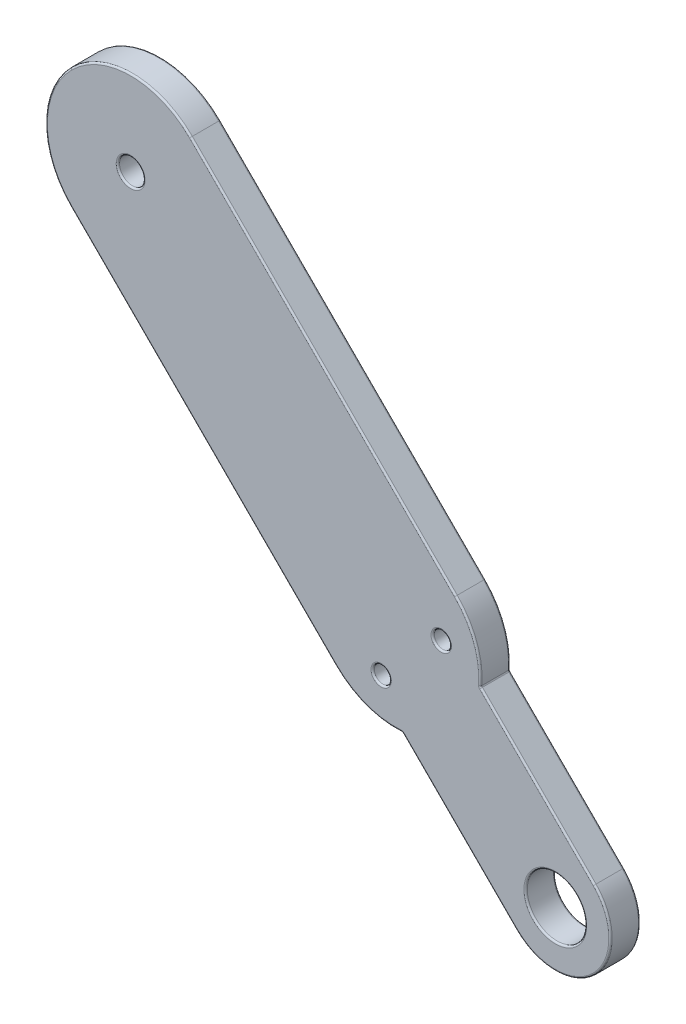
SolidWorks part; units mm, degrees
ref_plane "Front Plane" through (0, 0, 0) normal (0, 0, 1) x (1, 0, 0)
ref_plane "Top Plane" through (0, 0, 0) normal (0, 1, 0) x (1, 0, 0)
ref_plane "Right Plane" through (0, 0, 0) normal (1, 0, 0) x (0, 0, -1)
sketch "Sketch1" plane through (0, 0, 0) normal (0, 0, 1) x (1, 0, 0)
  line L0 (-100, 0) -> (100, 0) construction
  line L1 (-100, 0) -> (0, 100) construction
  line L2 (0, 100) -> (100, 0) construction
  line L3 (0, 0) -> (-50, 50) construction
  line L4 (-50, 50) -> (0, 0) construction
  line L5 (-40, 60) -> (40, 60) construction
  line L6 (0, 100) -> (0, 60) construction
  circle A0 centre (-100, 0) radius 20
  circle A1 centre (0, 0) radius 20
  circle A2 centre (100, 0) radius 20
  point P5 (0, 0)
  dimension "D5" = 40
  dimension "D1" = 200
  dimension "D2" = 90
  dimension "D3" = 90
  dimension "D4" = 80
sketch "Sketch2" plane through (0, 0, 0) normal (0, 0, 1) x (1, 0, 0)
  line L0 (-56.5165, 43.4835) -> (-40, 60) construction
  line L1 (-100, 0) -> (0, 100) construction
  line L2 (-40, 60) -> (40, 60) construction
  line L3 (40, 60) -> (86.565, 13.435) construction
  line L4 (0, 100) -> (100, 0) construction
  line L5 (-49.4454, 36.4124) -> (-35.8579, 50)
  line L6 (-35.8579, 50) -> (35.8579, 50)
  line L7 (35.8579, 50) -> (79.4939, 6.364)
  line L8 (-63.5876, 50.5546) -> (-44.1421, 70)
  line L9 (-44.1421, 70) -> (44.1421, 70)
  line L10 (44.1421, 70) -> (93.636, 20.5061)
  line L11 (-63.5876, 50.5546) -> (-49.4454, 36.4124)
  line L12 (93.636, 20.5061) -> (79.4939, 6.364)
  line L13 (81.9688, 8.8388) -> (95.4038, -4.5962)
  line L14 (91.1612, 18.0312) -> (104.5962, 4.5962)
  line L15 (75.9584, 9.8995) -> (90.1005, 24.0416) construction
  line L16 (0, 100) -> (0, 60) construction
  line L17 (-6, 70) -> (-3.4326, 85.5452)
  line L18 (6, 70) -> (3.4532, 85.4203)
  circle A0 centre (100, 0) radius 3.5
  circle A1 centre (100, 0) radius 10 construction
  arc A2 (95.4038, -4.5962) -> (104.5962, 4.5962) centre (100, 0) ccw
  circle A3 centre (100, 0) radius 0.5
  circle A4 centre (100, 0) radius 6.5 construction
  circle A5 centre (79.4939, 13.435) radius 1.8428
  circle A6 centre (86.565, 20.5061) radius 1.8428
  circle A7 centre (0, 60) radius 1.5
  circle A8 centre (0, 84.85) radius 1.5
  arc A9 (3.4532, 85.4203) -> (-3.4532, 85.4203) centre (0, 84.85) ccw
  circle A10 centre (0, 84.85) radius 3.5 construction
  circle A11 centre (-50, 50) radius 1.5
  dimension "D4" = 20
  dimension "D5" = 7
  dimension "D11" = 3
  dimension "D15" = 3
  dimension "D3" = 27.5
  dimension "D8" = 19
  dimension "D9" = 5
  dimension "D10" = 5
  dimension "5" = 5
  dimension "D12" = 14.85
  dimension "D7" = 6
  dimension "D14" = 6
  dimension "D1" = 10
  dimension "D2" = 10
  dimension "D6" = 3
  dimension "D13" = 2
sketch "Sketch3" plane through (0, 0, 0) normal (0, 0, 1) x (1, 0, 0)
  line L0 (-100, 0) -> (100, 0) construction
  line L1 (-14.1421, 19.799) -> (-12.7279, 21.2132) construction
  line L2 (-21.2132, 12.7279) -> (-19.799, 14.1421) construction
  line L3 (-50, 50) -> (-48.9393, 48.9393) construction
  line L4 (-50, 35.8579) -> (-64.1421, 50)
  line L6 (-50, 35.8579) -> (-20.5061, 6.364)
  line L7 (-64.1421, 50) -> (-50, 64.1421)
  line L8 (-50, 64.1421) -> (-6.364, 20.5061)
  line L9 (-81.6799, 4.1779) -> (-50, 35.8579) construction
  line L10 (-95.8221, 18.3201) -> (-50, 64.1421) construction
  line L12 (-20.5061, 6.364) -> (-18.0312, 8.8388)
  line L15 (-18.0312, 8.8388) -> (-4.5962, -4.5962)
  line L16 (-8.8388, 18.0312) -> (4.5962, 4.5962)
  line L17 (-88.751, 11.249) -> (-50, 50) construction
  line L19 (-8.8388, 18.0312) -> (-6.364, 20.5061)
  line L21 (-51.0607, 48.9393) -> (-50, 50) construction
  line L23 (-50, 50) -> (-13.435, 13.435) construction
  circle A3 centre (0, 0) radius 3.5
  arc A4 (-4.5962, -4.5962) -> (4.5962, 4.5962) centre (0, 0) ccw
  circle A7 centre (0, 0) radius 6.5 construction
  circle A10 centre (-20.5061, 13.435) radius 1
  circle A11 centre (-13.435, 20.5061) radius 1
  circle A12 centre (-50, 50) radius 1.5 construction
  circle A13 centre (-50, 50) radius 1.5
  dimension "D8" = 19
  dimension "D12" = 5
  dimension "D13" = 5
  dimension "D15" = 5
  dimension "D3" = 3
  dimension "D5" = 10
  dimension "D6" = 10
sketch "Sketch4" plane through (0, 0, 0) normal (0, 0, 1) x (1, 0, 0)
  line L1 (57.5, 96.35) -> (57.5, 86.35)
  line L2 (57.5, 86.35) -> (44.1421, 70)
  line L3 (44.1421, 70) -> (-44.1421, 70)
  line L4 (-44.1421, 70) -> (-57.5, 86.35)
  line L5 (-57.5, 86.35) -> (-57.5, 96.35)
  line L7 (-57.5, 96.35) -> (57.5, 96.35)
  line L8 (-4, 60) -> (-4, 70)
  line L9 (4, 60) -> (4, 70)
  line L10 (-22.4799, 87.85) -> (22.5201, 87.85) construction
  line L11 (-22.4799, 92.35) -> (22.5201, 92.35)
  line L12 (-22.4799, 83.35) -> (22.5201, 83.35)
  circle A0 centre (0, 60) radius 1.5 construction
  circle A1 centre (0, 60) radius 1.5
  arc A2 (-4, 60) -> (4, 60) centre (0, 60) ccw
  circle A3 centre (0, 60) radius 4 construction
  arc A4 (-22.4799, 92.35) -> (-22.4799, 83.35) centre (-22.4799, 87.85) ccw
  arc A5 (22.5201, 83.35) -> (22.5201, 92.35) centre (22.5201, 87.85) ccw
  circle A6 centre (0, 84.85) radius 1.5 construction
  point P0 (0, 96.35)
  point P22 (0.0201, 87.85)
  dimension "D1" = 115
  dimension "D2" = 10
  dimension "D4" = 45
  dimension "D5" = 9
  dimension "D6" = 45
  dimension "D7" = 4
  dimension "D3" = 2.5
extrude "Boss-Extrude1" add sketch "Sketch3" along normal blind 3.5
fillet "Fillet1" radius 10 4 edges at (-20.5061, 6.364, 1.75) (-6.364, 20.5061, 1.75) (-64.1421, 50, 1.75) (-50, 64.1421, 1.75)
fillet "Fillet2" radius 0.2 28 edges at (-48.5, 50, 0) (-48.5, 50, 3.5) (-12.435, 20.5061, 0) (-12.435, 20.5061, 3.5) (-19.5061, 13.435, 0) (-19.5061, 13.435, 3.5) (3.5, 0, 0) (3.5, 0, 3.5) (-41.4754, 27.3332, 0) (-11.3137, 2.1213, 0) (4.5962, -4.5962, 0) (-2.1213, 11.3137, 0) (-27.3332, 41.4754, 0) (-41.4754, 27.3332, 3.5) (-11.3137, 2.1213, 3.5) (4.5962, -4.5962, 3.5) (-2.1213, 11.3137, 3.5) (-8.8388, 18.0312, 1.75) (-18.0312, 8.8388, 1.75) (-50, 60, 0) (-60, 50, 0) (-9.4279, 22.2732, 0) (-22.2732, 9.4279, 0) (-50, 60, 3.5) (-60, 50, 3.5) (-9.4279, 22.2732, 3.5) (-22.2732, 9.4279, 3.5) (-27.3332, 41.4754, 3.5)
